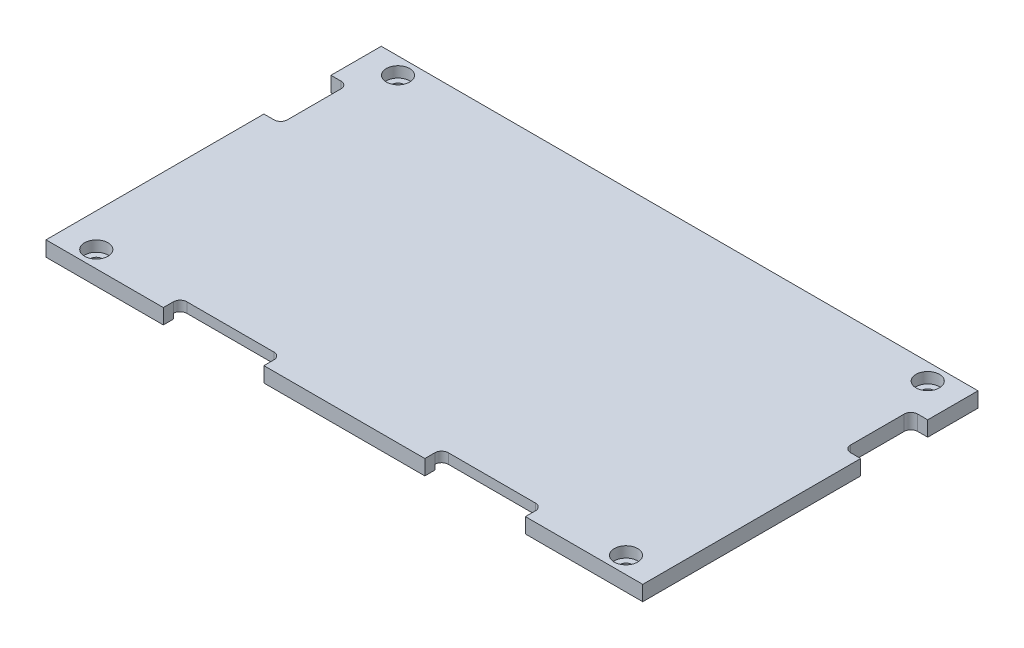
SolidWorks part; units mm, degrees
ref_plane "Ebene vorne" through (0, 0, 0) normal (0, 0, 1) x (1, 0, 0)
ref_plane "Ebene oben" through (0, 0, 0) normal (0, 1, 0) x (1, 0, 0)
ref_plane "Ebene rechts" through (0, 0, 0) normal (1, 0, 0) x (0, 0, -1)
sketch "Skizze1" plane through (0, 0, 0) normal (0, 1, 0) x (1, 0, 0)
  line L1 (0, 0) -> (-89, 0)
  line L2 (0, 0) -> (0, 50)
  line L3 (0, 50) -> (-89, 50)
  line L4 (-89, 0) -> (-89, 50)
  dimension "D1" = 89
  dimension "D2" = 50
extrude "Aufsatz-Linear austragen1" add sketch "Skizze1" along normal blind 4.5
sketch "Skizze3" plane through (0, 4.5, 0) normal (0, 1, 0) x (1, 0, 0)
  line L1 (0, 0) -> (0, 50) construction
  line L2 (-19, 3) -> (-3, 3)
  line L3 (-19, 3) -> (-19, 15)
  line L4 (-19, 15) -> (-3, 15)
  line L5 (-3, 3) -> (-3, 15)
  line L6 (-19, 3) -> (-3, 15) construction
  line L7 (-19, 15) -> (-3, 3) construction
  line L8 (-89, 0) -> (0, 0) construction
  point P0 (-11, 9)
  dimension "D1" = 3
  dimension "D3" = 12
  dimension "D2" = 3
  dimension "D4" = 16
extrude "Schnitt-Linear austragen2" cut sketch "Skizze3" against normal through all
fillet "Verrundung1" radius 2 4 edges at (-19, 2.25, -3) (-3, 2.25, -3) (-3, 2.25, -15) (-19, 2.25, -15)
pattern_linear "Lineares Muster1" count 3 spacing 16 along (0, 0, -1) count 4 spacing 20 along (-1, 0, 0) of "Schnitt-Linear austragen2", "Verrundung1"
sketch "Skizze2" plane through (0, 4.5, 0) normal (0, 1, 0) x (1, 0, 0)
  line L0 (0, 0) -> (0, 50) construction
  line L1 (-89, 0) -> (0, 0) construction
  circle A0 centre (-79, 45) radius 5
  dimension "D1" = 10
  dimension "D2" = 79
  dimension "D3" = 45
extrude "Aufsatz-Linear austragen2" add sketch "Skizze2" against normal up to surface (4.5 mm away) up to face at (-11, 0, -25)
hole_wizard "Stirnsenkung für M3 Flachkopfschraube mit Schlitz1" positions "Skizze4" profile "Skizze5" counterbore size "M3" standard "DIN" end condition through all
sketch "Skizze4" plane through (0, 4.5, 0) normal (0, 1, 0) x (1, 0, 0)
  line L0 (0, 50) -> (-89, 50) construction
  point P0 (-79, 45)
  dimension "D1" = 10
  dimension "D2" = 5
sketch "Skizze5" plane through (-79, 4.5, -45) normal (1, 0, 0) x (0, 0, 1)
  line L0 (0, 0) -> (0, 4.5)
  line L1 (0, 4.5) -> (1.7, 4.5)
  line L3 (1.7, 4.5) -> (1.7, 3.2)
  line L4 (1.7, 3.2) -> (3.5, 3.2)
  line L5 (3.5, 3.2) -> (3.5, 0)
  line L7 (3.5, 0) -> (0, 0)
  line L11 (0, -6.35) -> (0, 107.95) construction
  dimension "Bohrerdurchmesser" = 3.4
  dimension "Bohrungstiefe" = 4.5
  dimension "Senkdurchmesser2" = 7
  dimension "Senktiefe2" = 3.2
fillet "Verrundung3" radius 3 2 edges at (-79, 2.25, -40) (-74.4174, 2.25, -47)
sketch "Skizze6" plane through (0, 0, 0) normal (0, -1, 0) x (1, 0, 0)
  line L0 (-79, -29) -> (-79, -21) construction
  line L1 (0, 0) -> (-79, 0)
  line L2 (0, 0) -> (0, -47)
  line L3 (0, -47) -> (-71.0627, -47)
  line L4 (-79, 0) -> (-79, -37)
  line L5 (-71.0627, -37) -> (-79, -37)
  line L6 (-71.0627, -37) -> (-71.0627, -47)
  line L11 (-45, -47) -> (-57, -47) construction
  line L12 (-65, -47) -> (-71.0627, -47) construction
extrude "Schnitt-Linear austragen3" cut sketch "Skizze6" against normal blind 1.5
sketch "Skizze7" plane through (0, 1.5, 0) normal (0, -1, 0) x (1, 0, 0)
  line L0 (-79, 0) -> (0, 0)
  line L1 (0, 0) -> (0, -47)
  line L6 (0, -50) -> (0, -47)
  line L7 (0, -47) -> (-71.0627, -47)
  line L8 (-79, -37.5838) -> (-79, 0)
  line L9 (-79, 0) -> (-89, 0)
  line L10 (-89, 0) -> (-89, -50)
  line L11 (-89, -50) -> (0, -50)
  line L13 (0, -47) -> (-71.0627, -47)
  line L14 (-79, -37.5838) -> (-79, 0)
  arc A3 (-74.0392, -44.375) -> (-71.0627, -47) centre (-71.0627, -44) ccw
  arc A4 (-74.0392, -44.375) -> (-77.125, -40.3649) centre (-79, -45) ccw
  arc A5 (-79, -37.5838) -> (-77.125, -40.3649) centre (-76, -37.5838) ccw
  arc A6 (-74.0392, -44.375) -> (-71.0627, -47) centre (-71.0627, -44) ccw
  arc A7 (-74.0392, -44.375) -> (-77.125, -40.3649) centre (-79, -45) ccw
  arc A8 (-79, -37.5838) -> (-77.125, -40.3649) centre (-76, -37.5838) ccw
  dimension "D1" = 0
extrude "Aufsatz-Linear austragen3" add sketch "Skizze7" against normal up to surface (3 mm away) up to face at (-79, 4.5, -41.5)
mirror "Spiegeln1" about plane through (0, 4.5, 0) normal (0, 0, -1) of bodies 124 115
sketch "Skizze8" plane through (0, 0, 0) normal (0, -1, 0) x (1, 0, 0)
  line L0 (0, 50) -> (-89, 50) construction
  line L1 (-24, 55) -> (-54, 55)
  line L2 (-24, 55) -> (-24, 45)
  line L3 (-24, 45) -> (-54, 45)
  line L4 (-54, 55) -> (-54, 45)
  line L5 (-24, 55) -> (-54, 45) construction
  line L6 (-24, 45) -> (-54, 55) construction
  line L7 (-89, -50) -> (-89, 50) construction
  line L8 (0, -50) -> (-89, -50) construction
  line L9 (-94, -35) -> (-84, -35)
  line L10 (-94, -35) -> (-94, -15)
  line L11 (-94, -15) -> (-84, -15)
  line L12 (-84, -35) -> (-84, -15)
  line L13 (-94, -35) -> (-84, -15) construction
  line L14 (-94, -15) -> (-84, -35) construction
  point P0 (-39, 50)
  point P9 (-89, -25)
  dimension "D1" = 30
  dimension "D2" = 50
  dimension "D3" = 5
  dimension "D4" = 5
  dimension "D5" = 20
  dimension "D6" = 15
extrude "Schnitt-Linear austragen4" cut sketch "Skizze8" against normal through all
fillet "Verrundung4" radius 2 4 edges at (-24, 3, 45) (-54, 3, 45) (-84, 2.25, -15) (-84, 2.25, -35)
mirror "Spiegeln2" about plane through (0, 4.5, 0) normal (-1, 0, 0) of bodies 125 116
